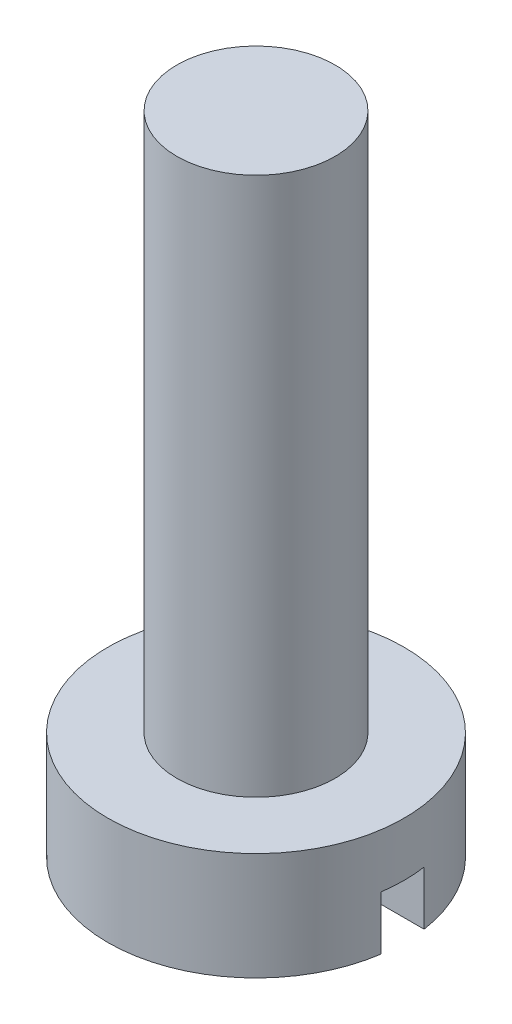
SolidWorks part; units mm, degrees
ref_plane "Front Plane" through (0, 0, 0) normal (0, 0, 1) x (1, 0, 0)
ref_plane "Top Plane" through (0, 0, 0) normal (0, 1, 0) x (1, 0, 0)
ref_plane "Right Plane" through (0, 0, 0) normal (1, 0, 0) x (0, 0, -1)
sketch "Sketch1" plane through (0, 0, 0) normal (0, 1, 0) x (1, 0, 0)
  line L1 (0, 0.4) -> (3.2327, 0.4)
  line L2 (3.2327, 0.4) -> (3.2327, -0.4)
  line L3 (3.2327, -0.4) -> (-3.2378, -0.4)
  line L4 (-3.2378, -0.4) -> (-3.2378, 0.4)
  line L5 (-3.2378, 0.4) -> (0, 0.4)
  circle A0 centre (0, 0) radius 2.75
  circle A1 centre (0, 0) radius 1.47
extrude "Boss-Extrude1" add sketch "Sketch1" along normal blind 2 contours A1 L1 A0 L5 | L1 A1 L5 | L3 A1 L1 L5 | L3 A1 | A1 L3 A0 | A1 L3 A0 L1 | A1 L5 A0 L3 region at (0, 0, -0.845) region at (0, 0, 0) region at (0, 0, -1.5482) region at (2.0959, 0, 0) region at (-2.0959, 0, 0) region at (0, 0, 1.5482) region at (0, 0, 0.845)
extrude "Cut-Extrude1" cut sketch "Sketch1<3>" along normal blind 1 contours A1 L3 A0 L1 | A1 L5 A0 L3 | L3 A1 L1 L5 region at (0, 0, 0) region at (2.0959, 0, 0) region at (-2.0959, 0, 0)
sketch "Sketch1<3>" plane through (0, 0, 0) normal (0, 1, 0) x (1, 0, 0) same geometry as "Sketch1"
extrude "Boss-Extrude2" add sketch "Sketch1<4>" along normal blind 10 from surface contours L1 A1 L5 | L3 A1 L1 L5 | L3 A1 region at (0, 0, -0.845) region at (0, 0, 0) region at (0, 0, 0.845) starting at face at (0, 2, 2.75)
sketch "Sketch1<4>" plane through (0, 0, 0) normal (0, 1, 0) x (1, 0, 0) same geometry as "Sketch1"
